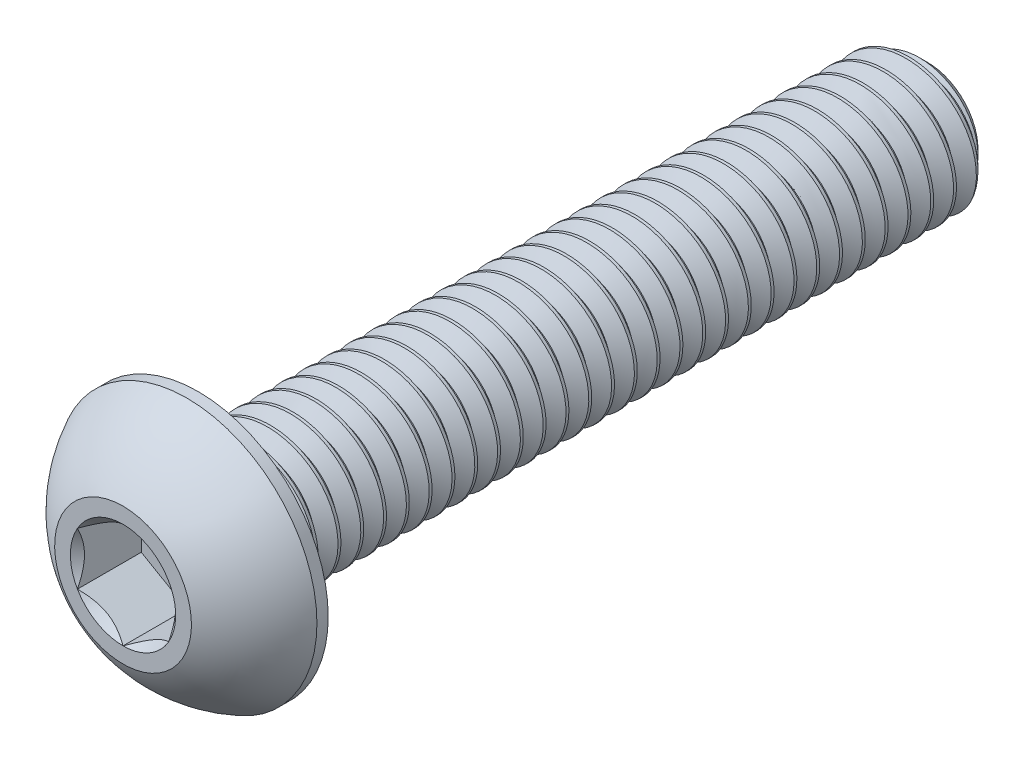
SolidWorks part; units mm, degrees
material "Plain Carbon Steel"
ref_plane "Front Plane" through (0, 0, 0) normal (0, 0, 1) x (1, 0, 0)
ref_plane "Top Plane" through (0, 0, 0) normal (0, 1, 0) x (1, 0, 0)
ref_plane "Right Plane" through (0, 0, 0) normal (1, 0, 0) x (0, 0, -1)
sketch "Sketch1" plane through (0, 0, 0) normal (1, 0, 0) x (0, 0, -1)
  line L0 (-8.825, 0) -> (8.825, 0) construction
  line L1 (-7.175, 2.85) -> (-7.175, -2.85) construction
  line L2 (8.825, 1.5) -> (8.825, -1.5) construction
  line L3 (8.7937, 1.5541) -> (9.0437, 1.1211) construction
  line L4 (9.0437, 1.1211) -> (9.2937, 1.5541) construction
  line L5 (9.2937, 1.5541) -> (8.7937, 1.5541) construction
  line L6 (8.825, 1.5) -> (9.2625, 1.5) construction
  line L7 (9.0437, 1.5541) -> (9.0437, 1.5) construction
  line L8 (9.0437, 1.5) -> (9.0437, 1.1752) construction
  line L9 (9.0437, 1.1752) -> (9.0437, 1.1211) construction
  line L10 (9.0125, 1.1752) -> (9.075, 1.1752)
  line L11 (8.8094, 1.5271) -> (9.2781, 1.5271)
  line L12 (9.075, 1.1752) -> (9.2781, 1.5271)
  line L13 (9.0125, 1.1752) -> (8.8094, 1.5271)
  line L14 (-8.825, 1) -> (-8.825, -1) construction
  line L15 (8.825, 1.5) -> (-7.175, 1.5) construction
  point P3 (-7.175, 0)
  point P6 (-7.425, 0)
  point P21 (9.0437, 1.5271)
  point P24 (-7.4225, 2.85)
  point P25 (7.575, -1.5)
  point P26 (-8.825, 1.5)
  dimension "Head Height" = 1.65
  dimension "Length" = 16
  dimension "Head Dia" = 5.7
  dimension "Thread Dia" = 3
  dimension "Pitch" = 0.5
  dimension "Drive Size" = 2
  dimension "D1" = 1.4
  dimension "D3" = 0.2475
  dimension "D4" = 1.25
sketch "Sketch2" plane through (0, 0, 0) normal (1, 0, 0) x (0, 0, -1)
  line L0 (-8.825, 0) -> (8.825, 0)
  line L1 (8.825, 0) -> (8.825, 1.1)
  line L2 (8.825, 1.5) -> (8.825, -1.5) construction
  line L3 (8.825, 1.1) -> (8.425, 1.5)
  line L4 (8.425, 1.5) -> (-7.175, 1.5)
  line L5 (-7.175, 2.85) -> (-7.175, -2.85) construction
  line L6 (-7.175, 1.5) -> (-7.175, 2.85)
  line L7 (-7.175, 2.85) -> (-7.4225, 2.85)
  line L8 (8.825, 1.5) -> (9.2625, 1.5) construction
  line L9 (-8.825, 0) -> (-8.825, 1.5)
  arc A0 (-8.825, 1.5) -> (-7.4225, 2.85) centre (-6.0302, 0) cw
  dimension "D1" = 0.4
  dimension "D2" = 45
revolve "Revolve1" add sketch "Sketch2" angle 360 about L0
sketch "Sketch3" plane through (0, 0, 8.825) normal (0, 0, 1) x (1, 0, 0)
  line L1 (0, 1.1547) -> (-1, 0.5774)
  line L2 (-1, 0.5774) -> (-1, -0.5774)
  line L3 (-1, -0.5774) -> (0, -1.1547)
  line L4 (0, -1.1547) -> (1, -0.5774)
  line L5 (1, -0.5774) -> (1, 0.5774)
  line L6 (1, 0.5774) -> (0, 1.1547)
  circle A0 centre (0, 0) radius 1 construction
  dimension "D1" = 2
extrude "Cut-Extrude1" cut sketch "Sketch3" against normal up to vertex (1.4 mm away) up to point (0, 0, 7.425)
sketch "Sketch4" plane through (0, 0, 8.825) normal (0, 0, 1) x (1, 0, 0)
  circle A0 centre (0, 0) radius 1.1547
extrude "Cut-Extrude2" cut sketch "Sketch4" against normal blind 10 draft 45
split "Split1" bodies to split 106 resulting bodies 107 108 split by face at (2.85, 0, 7.175)
sketch "Sketch5" plane through (0, 0, -8.825) normal (0, 0, -1) x (-1, 0, 0)
  circle A0 centre (0, 0) radius 1.5 construction
  circle A1 centre (0, 0) radius 1.5
curve "Helix/Spiral1" pitch 0.5 height 16.5 radius 1.5 centre (0, 0, -8.825) axis (0, 0, 1) start towards (0, 1, 0)
sketch "Sketch6" plane through (0, 0, 0) normal (1, 0, 0) x (0, 0, -1)
  line L0 (9.0125, 1.1752) -> (9.075, 1.1752) construction
  line L1 (9.0125, 1.1752) -> (8.8094, 1.5271) construction
  line L2 (8.8094, 1.5271) -> (9.2781, 1.5271) construction
  line L3 (9.075, 1.1752) -> (9.2781, 1.5271) construction
  line L4 (9.0125, 1.1752) -> (9.075, 1.1752)
  line L5 (9.0125, 1.1752) -> (8.8094, 1.5271)
  line L6 (8.8094, 1.5271) -> (9.2781, 1.5271)
  line L7 (9.075, 1.1752) -> (9.2781, 1.5271)
sweep "Cut-Sweep1" cut profiles "Sketch6" path "Helix/Spiral1" align with end faces yes
sketch "Sketch7" plane through (0, 0, 7.175) normal (0, 0, -1) x (-1, 0, 0)
  circle A1 centre (0, 0) radius 1.5
  circle A2 centre (0, 0) radius 1.5
  dimension "D1" = 0
extrude "Boss-Extrude1" add sketch "Sketch7" along normal blind 10 draft 30
equation "\"D2@Sketch1\" = \"Pitch@Sketch1\" / 8"
equation "\"D1@Sketch1\"=\"Drive Size@Sketch1\"*.7"
equation "\"D3@Sketch1\"=\"Head Height@Sketch1\"*.15"
equation "\"D1@Sketch2\"=\"Pitch@Sketch1\"*.8"
equation "\"D1@Sketch3\"=\"Drive Size@Sketch1\""
equation "\"D4@Helix/Spiral1\"=\"Pitch@Sketch1\""
equation "\"D3@Helix/Spiral1\"=\"Length@Sketch1\"+\"Pitch@Sketch1\""
equation "\"D4@Sketch1\"=\"Pitch@Sketch1\"*2.5"
